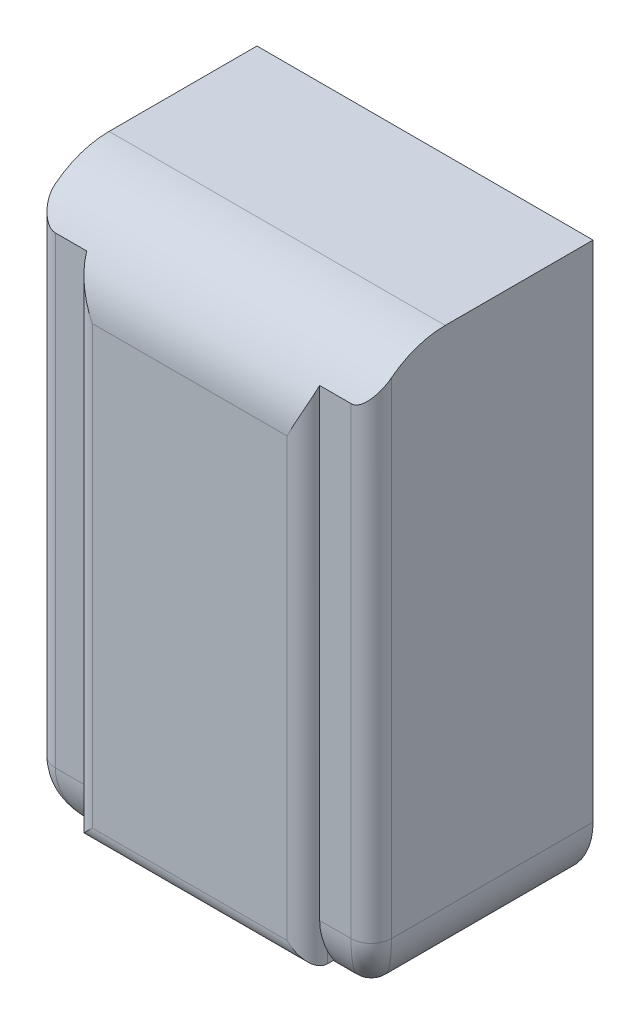
SolidWorks part; units mm, degrees
material "C355.0-T61 Moulage permanent (SS)"
ref_plane "Plan de face" through (0, 0, 0) normal (0, 0, 1) x (1, 0, 0)
ref_plane "Plan de dessus" through (0, 0, 0) normal (0, 1, 0) x (1, 0, 0)
ref_plane "Plan de droite" through (0, 0, 0) normal (1, 0, 0) x (0, 0, -1)
sketch "Esquisse1" plane through (0, 0, 0) normal (0, 0, 1) x (1, 0, 0)
  line L1 (25, -42.5) -> (-25, -42.5)
  line L2 (25, -42.5) -> (25, 42.5)
  line L3 (25, 42.5) -> (-25, 42.5)
  line L4 (-25, -42.5) -> (-25, 42.5)
  line L5 (25, -42.5) -> (-25, 42.5) construction
  line L6 (25, 42.5) -> (-25, -42.5) construction
  point P0 (0, 0)
  dimension "D1" = 50
  dimension "D2" = 85
extrude "Boss.-Extru.1" add sketch "Esquisse1" along normal blind 33
sketch "Esquisse2" plane through (0, 0, 33) normal (0, 0, 1) x (1, 0, 0)
  line L0 (25, 42.5) -> (-25, 42.5) construction
  line L1 (-17.5, 42.5) -> (17.5, 42.5)
  line L2 (-17.5, 42.5) -> (-17.5, -38.5)
  line L3 (-17.5, -38.5) -> (17.5, -38.5)
  line L4 (17.5, 42.5) -> (17.5, -38.5)
  line L5 (0, 42.5) -> (0, 0) construction
  line L6 (-25, -42.5) -> (25, -42.5) construction
  dimension "D1" = 4
  dimension "D2" = 35
extrude "Boss.-Extru.2" add sketch "Esquisse2" along normal blind 2
fillet "Congé1" radius 10 3 edges at (0, -42.5, 33) (25, -42.5, 16.5) (-25, -42.5, 16.5)
fillet "Congé2" radius 3 7 edges at (22.0711, -39.5711, 30.0711) (-22.0711, -39.5711, 30.0711) (25, 5, 33) (17.5, 2, 35) (-25, 5, 33) (-17.5, 2, 35) (0, -38.5, 35)
fillet "Congé4" radius 13 1 edges at (0, 42.5, 35)
